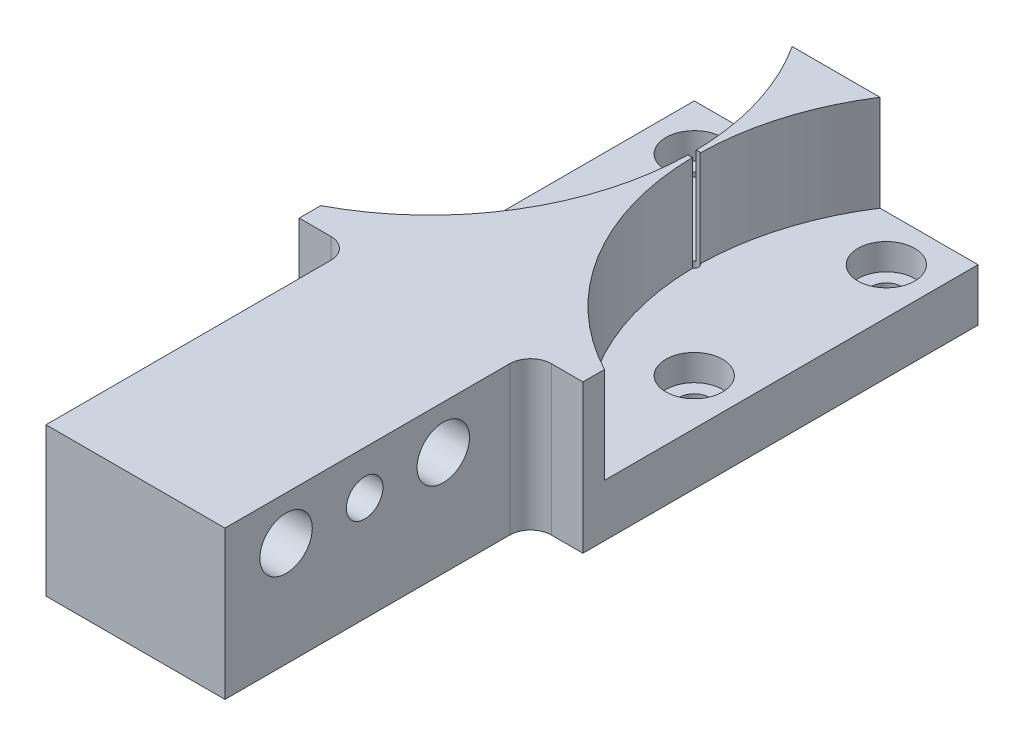
SolidWorks part; units mm, degrees
ref_plane "Front Plane" through (0, 0, 0) normal (0, 0, 1) x (1, 0, 0)
ref_plane "Top Plane" through (0, 0, 0) normal (0, 1, 0) x (1, 0, 0)
ref_plane "Right Plane" through (0, 0, 0) normal (1, 0, 0) x (0, 0, -1)
sketch "Sketch1" plane through (0, 0, 0) normal (0, 1, 0) x (1, 0, 0)
  line L0 (-16.25, 0) -> (16.25, 0)
  line L1 (-16.25, 0) -> (-16.25, -80.25)
  line L2 (-16.25, -80.25) -> (16.25, -80.25)
  line L3 (16.25, -80.25) -> (16.25, 0)
  line L4 (-0.45, -16.25) -> (-0.25, -16.25) construction
  line L5 (0.45, -16.25) -> (0.25, -16.25) construction
  line L6 (-16.25, -52.25) -> (16.25, -52.25) construction
  line L7 (11, -27.25) -> (-11, -27.25) construction
  line L8 (11, -27.25) -> (11, -5.25) construction
  line L9 (11, -5.25) -> (-11, -5.25) construction
  line L10 (-11, -27.25) -> (-11, -5.25) construction
  line L11 (11, -27.25) -> (-11, -5.25) construction
  line L12 (11, -5.25) -> (-11, -27.25) construction
  line L13 (-16.25, -58.25) -> (16.25, -58.25) construction
  line L14 (-16.25, -76.25) -> (16.25, -76.25) construction
  line L15 (-16.25, -70.25) -> (16.25, -70.25) construction
  line L16 (-16.25, -66.75) -> (16.25, -66.75) construction
  line L17 (-16.25, -61.75) -> (16.25, -61.75) construction
  line L18 (0, -52.25) -> (0, -58.25) construction
  line L19 (0, -66.75) -> (0, -61.75) construction
  line L20 (0, -70.25) -> (0, -76.25) construction
  line L21 (0, -58.25) -> (0, -66.75) construction
  line L22 (0, -61.75) -> (0, -70.25) construction
  line L23 (-16.25, -48.25) -> (16.25, -48.25) construction
  line L24 (0, -52.25) -> (0, -48.25) construction
  line L25 (0, -76.25) -> (0, -80.25) construction
  line L26 (0, -16.25) -> (0, 15.25) construction
  line L27 (-12.775, 15.25) -> (12.775, 15.25) construction
  line L28 (-30.25, -46.25) -> (-30.25, -48.25) construction
  arc A0 (-16.25, -42.783) -> (-5.0322, 0) centre (-30.25, -16.25) ccw construction
  circle A1 centre (0, -16.25) radius 0.45 construction
  arc A2 (5.0322, 0) -> (16.25, -42.783) centre (30.25, -16.25) ccw construction
  circle A3 centre (-11, -5.25) radius 5.25 construction
  circle A4 centre (-11, -5.25) radius 3.25 construction
  circle A5 centre (-11, -5.25) radius 1.5 construction
  arc A6 (-16.25, -42.783) -> (-5.0322, 0) centre (-30.25, -16.25) cw construction
  circle A7 centre (-12.775, 15.25) radius 5 construction
  circle A8 centre (12.775, 15.25) radius 5 construction
  point P43 (0, -55.25)
  point P44 (0, -73.25)
  dimension "D1" = 0.9
  dimension "D4" = 2
  dimension "D5" = 6.5
  dimension "D6" = 3
  dimension "D7" = 30
  dimension "D17" = 10
  dimension "D2" = 0.2
  dimension "D3" = 22
  dimension "D8" = 32.5
  dimension "D9" = 4
  dimension "D10" = 6
  dimension "D11" = 18
  dimension "D12" = 5
  dimension "D13" = 2
  dimension "D15" = 31.5
  dimension "D16" = 25.55
  dimension "D18" = 3.5
extrude "Boss-Extrude1" add sketch "Sketch1" against normal blind 6
sketch "Sketch2" plane through (0, 0, 0) normal (0, 1, 0) x (1, 0, 0)
  line L0 (-5.0322, 0) -> (5.0322, 0)
  line L1 (-16.25, -42.783) -> (-16.25, -80.25)
  line L2 (-16.25, -80.25) -> (16.25, -80.25)
  line L3 (16.25, -80.25) -> (16.25, -42.783)
  arc A0 (5.0322, 0) -> (16.25, -42.783) centre (30.25, -16.25) ccw construction
  arc A1 (-16.25, -42.783) -> (-5.0322, 0) centre (-30.25, -16.25) ccw construction
  arc A2 (5.0322, 0) -> (16.25, -42.783) centre (30.25, -16.25) ccw
  arc A3 (-16.25, -42.783) -> (-5.0322, 0) centre (-30.25, -16.25) ccw
extrude "Boss-Extrude2" add sketch "Sketch2" along normal blind 11
sketch "Sketch3" plane through (16.25, 0, 0) normal (1, 0, 0) x (0, 0, -1)
  line L0 (-73.25, 11) -> (-73.25, 1) construction
  line L1 (-80.25, 11) -> (-42.783, 11) construction
  line L3 (-55.25, 11) -> (-55.25, 1) construction
  line L4 (-64.25, 11) -> (-64.25, 1) construction
  line L6 (-80.25, 0) -> (0, 0) construction
  line L7 (-66.75, 0) -> (-61.75, 0) construction
  point P20 (-64.25, 0)
  dimension "D1" = 10
hole_wizard "Ø6.0mm Dowel Hole1" positions "Sketch4" profile "Sketch5" hole size "Ø6.0" standard "ANSI Metric" end condition through all
sketch "Sketch4" plane through (16.25, 0, 0) normal (1, 0, 0) x (0, 0, -1)
  line L0 (-73.25, 11) -> (-73.25, 1) construction
  line L1 (-55.25, 11) -> (-55.25, 1) construction
  point P0 (-73.25, 6)
  point P4 (-55.25, 6)
sketch "Sketch5" plane through (16.25, 6, 73.25) normal (0, 1, 0) x (0, 0, -1)
  line L0 (0, 0) -> (0, 32.5)
  line L1 (0, 32.5) -> (3, 32.5)
  line L2 (3, 32.5) -> (3, 0)
  line L5 (3, 0) -> (0, 0)
  line L11 (0, -6.35) -> (0, 107.95) construction
  dimension "Thru Hole Dia." = 6
  dimension "Thru Hole Depth" = 32.5
hole_wizard "M5x0.8 Tapped Hole1" positions "Sketch6" profile "Sketch7" tap size "M5x0.8" standard "ANSI Metric" end condition through all
sketch "Sketch6" plane through (16.25, 0, 0) normal (1, 0, 0) x (0, 0, -1)
  line L0 (-64.25, 11) -> (-64.25, 1) construction
  point P0 (-64.25, 6)
sketch "Sketch7" plane through (16.25, 6, 64.25) normal (0, 1, 0) x (0, 0, -1)
  line L0 (0, 0) -> (0, 32.5)
  line L1 (0, 32.5) -> (2.1, 32.5)
  line L2 (2.1, 32.5) -> (2.1, 0)
  line L5 (2.1, 0) -> (0, 0)
  line L11 (0, -6.35) -> (0, 107.95) construction
  dimension "Thru Tap Drill Dia." = 4.2
  dimension "Thru Tap Drill Depth" = 32.5
cosmetic thread "Hole Thread1" parameters "D2"=5
hole_wizard "CBORE for M3 SHCS1" positions "Sketch8" profile "Sketch9" counterbore size "M3" standard "ANSI Metric" end condition through all
sketch "Sketch8" plane through (0, 0, 0) normal (0, 1, 0) x (1, 0, 0)
  point P0 (-11, -5.25)
  point P3 (11, -5.25)
  point P6 (11, -27.25)
  point P9 (-11, -27.25)
sketch "Sketch9" plane through (-11, 0, 5.25) normal (1, 0, 0) x (0, 0, 1)
  line L0 (0, 0) -> (0, 6)
  line L1 (0, 6) -> (1.7, 6)
  line L3 (1.7, 6) -> (1.7, 3)
  line L4 (1.7, 3) -> (3.25, 3)
  line L5 (3.25, 3) -> (3.25, 0)
  line L7 (3.25, 0) -> (0, 0)
  line L11 (0, -6.35) -> (0, 107.95) construction
  dimension "Thru Hole Dia." = 3.4
  dimension "Thru Hole Depth" = 6
  dimension "C'Bore Dia." = 6.5
  dimension "C'Bore Depth" = 3
hole_wizard "Ø1.0 (1) Diameter Hole1" positions "Sketch10" profile "Sketch11" hole size "Ø1.0" standard "ANSI Metric" end condition through all
sketch "Sketch10" plane through (0, 11, 0) normal (0, 1, 0) x (1, 0, 0)
  point P0 (0, -16.25)
sketch "Sketch11" plane through (0, 11, 16.25) normal (1, 0, 0) x (0, 0, 1)
  line L0 (0, 0) -> (0, 17)
  line L1 (0, 17) -> (0.5, 17)
  line L2 (0.5, 17) -> (0.5, 0)
  line L5 (0.5, 0) -> (0, 0)
  line L11 (0, -6.35) -> (0, 107.95) construction
  dimension "Thru Hole Dia." = 1
  dimension "Thru Hole Depth" = 17
sketch "Sketch12" plane through (0, -6, 0) normal (0, -1, 0) x (1, 0, 0)
  circle A0 centre (0, 16.25) radius 1.5
  dimension "D1" = 3
extrude "Cut-Extrude1" cut sketch "Sketch12" against normal blind 5
sketch "Sketch13" plane through (0, 11, 0) normal (0, 1, 0) x (1, 0, 0)
  line L0 (-16.25, 0) -> (-16.25, -80.25) construction
  line L1 (-16.25, -45.25) -> (-10.25, -45.25)
  line L2 (-16.25, -45.25) -> (-16.25, -80.25)
  line L3 (-16.25, -80.25) -> (-10.25, -80.25)
  line L4 (-10.25, -45.25) -> (-10.25, -80.25)
  line L5 (-16.25, -80.25) -> (16.25, -80.25) construction
  line L6 (16.25, -80.25) -> (16.25, 0) construction
  line L7 (16.25, -45.25) -> (10.25, -45.25)
  line L8 (16.25, -45.25) -> (16.25, -80.25)
  line L9 (16.25, -80.25) -> (10.25, -80.25)
  line L10 (10.25, -45.25) -> (10.25, -80.25)
  line L11 (-16.25, -48.25) -> (16.25, -48.25) construction
  arc A0 (-16.25, -42.783) -> (-0.2531, -16.6812) centre (-30.25, -16.25) ccw construction
  point P16 (-30.25, -16.25)
  dimension "D1" = 3
  dimension "D2" = 20
extrude "Cut-Extrude2" cut sketch "Sketch13" against normal through all
fillet "Fillet1" radius 2.3813 2 edges at (10.25, 2.5, 45.25) (-10.25, 2.5, 45.25)
